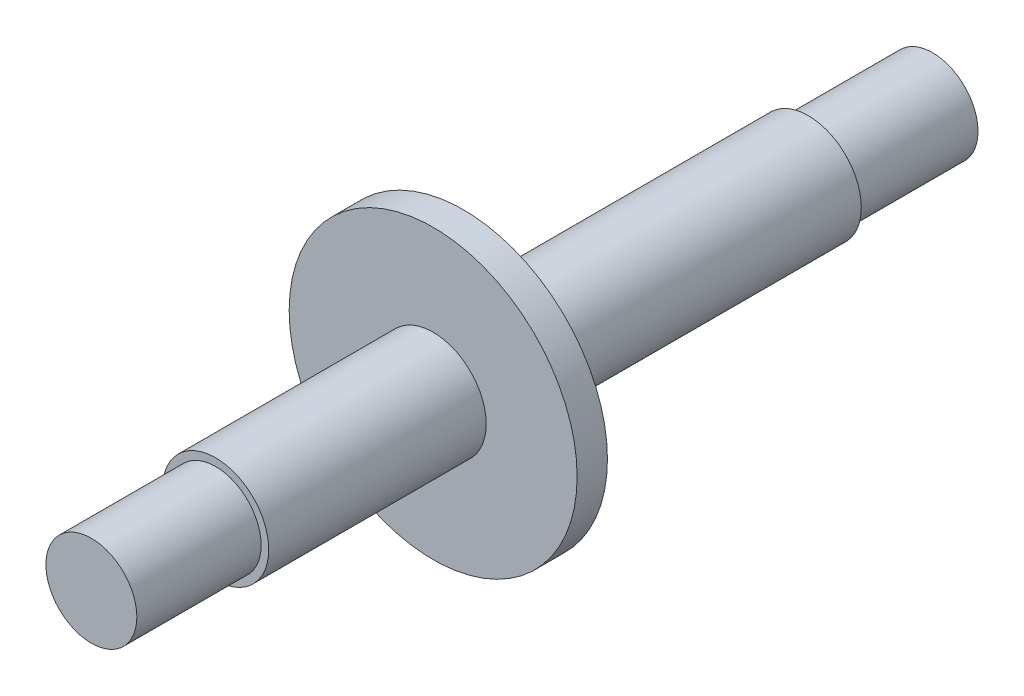
SolidWorks part; units mm, degrees
material "3.0205 (EN-AW 1200)"
ref_plane "Alzado" through (0, 0, 0) normal (0, 0, 1) x (1, 0, 0)
ref_plane "Planta" through (0, 0, 0) normal (0, 1, 0) x (1, 0, 0)
ref_plane "Vista lateral" through (0, 0, 0) normal (1, 0, 0) x (0, 0, -1)
sketch "Croquis1" plane through (0, 0, 0) normal (0, 0, 1) x (1, 0, 0)
  circle A0 centre (0, 0) radius 3
extrude "Saliente-Extruir1" add sketch "Croquis1" along normal blind 8.2
sketch "Croquis2" plane through (0, 0, 8.2) normal (0, 0, 1) x (1, 0, 0)
  circle A0 centre (0, 0) radius 3.5
extrude "Saliente-Extruir2" add sketch "Croquis2" along normal blind 22.75
sketch "Croquis3" plane through (0, 0, 30.95) normal (0, 0, 1) x (1, 0, 0)
  circle A0 centre (0, 0) radius 9.5
extrude "Saliente-Extruir3" add sketch "Croquis3" along normal blind 2
sketch "Croquis4" plane through (0, 0, 32.95) normal (0, 0, 1) x (1, 0, 0)
  circle A0 centre (0, 0) radius 3.5
extrude "Saliente-Extruir4" add sketch "Croquis4" along normal blind 14.35
sketch "Croquis5" plane through (0, 0, 47.3) normal (0, 0, 1) x (1, 0, 0)
  circle A0 centre (0, 0) radius 3
extrude "Saliente-Extruir5" add sketch "Croquis5" along normal blind 8.2
